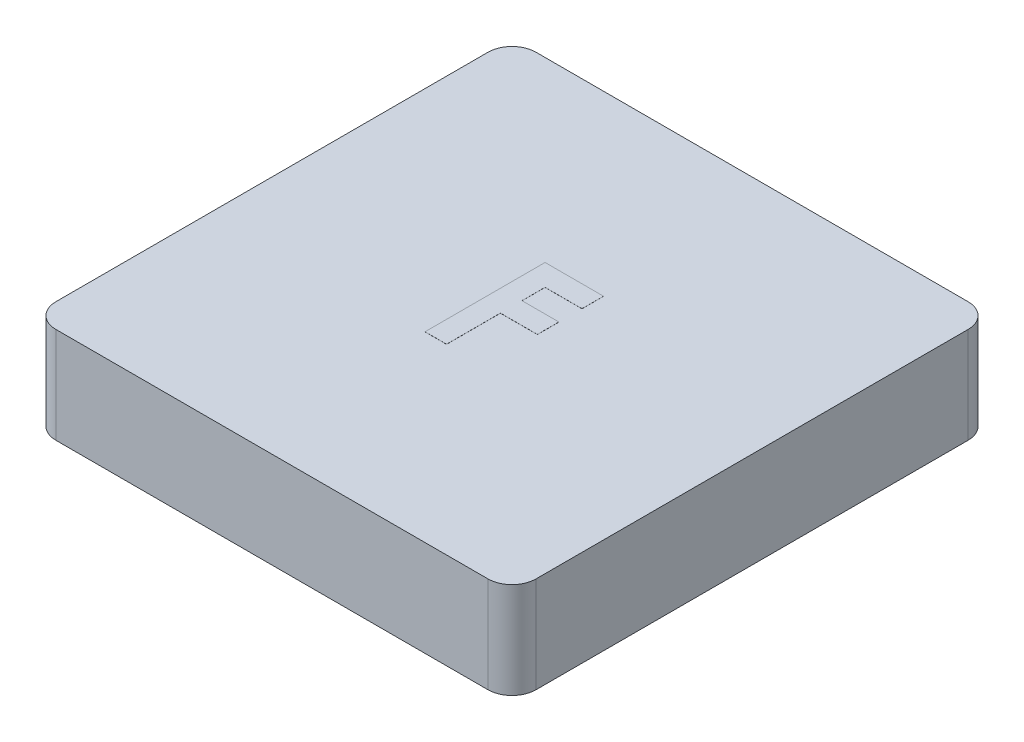
SolidWorks part; units mm, degrees
ref_plane "Front Plane" through (0, 0, 0) normal (0, 0, 1) x (1, 0, 0)
ref_plane "Top Plane" through (0, 0, 0) normal (0, 1, 0) x (1, 0, 0)
ref_plane "Right Plane" through (0, 0, 0) normal (1, 0, 0) x (0, 0, -1)
sketch "Sketch1" plane through (0, 0, 0) normal (0, 1, 0) x (1, 0, 0)
  line L0 (0, 0) -> (12.7, 0)
  line L1 (12.7, 0) -> (12.7, 12.7)
  line L2 (12.7, 12.7) -> (0, 12.7)
  line L3 (0, 12.7) -> (0, 0)
  dimension "D1" = 12.7
  dimension "D2" = 12.7
extrude "Boss-Extrude1" add sketch "Sketch1" along normal blind 2.54
fillet "Fillet1" radius 0.635 4 edges at (0, 1.27, -12.7) (12.7, 1.27, -12.7) (12.7, 1.27, 0) (0, 1.27, 0)
shell "Shell1" thickness 0.635 removed face at (6.35, 0, -6.35)
sketch "Sketch2" plane through (0, 1.905, 0) normal (0, -1, 0) x (-1, 0, 0)
  line L0 (-0.635, 6.35) -> (-12.065, 6.35) construction
  line L1 (-0.635, 12.065) -> (-0.635, 0.635) construction
  line L2 (-12.065, 0.635) -> (-12.065, 12.065) construction
  line L3 (-6.35, 0.635) -> (-6.35, 12.065) construction
  line L4 (-0.635, 0.635) -> (-12.065, 0.635) construction
  line L5 (-12.065, 12.065) -> (-0.635, 12.065) construction
  circle A0 centre (-6.35, 6.35) radius 2.54
  dimension "D1" = 5.08
extrude "Boss-Extrude2" add sketch "Sketch2" along normal up to surface (1.905 mm away) up to face at (6.35, 0, -6.35)
sketch "Sketch3" plane through (0, 2.54, 0) normal (0, 1, 0) x (1, 0, 0)
  line L0 (0, 12.065) -> (0, 0.635) construction
  line L1 (0.635, 0) -> (12.065, 0) construction
  text T0 "<b>F</b>"
  point P1 (0, 0)
  dimension "D1" = 5.207
  dimension "D2" = 4.826
extrude "Boss-Extrude3" add sketch "Sketch3" along normal blind 0.0025
